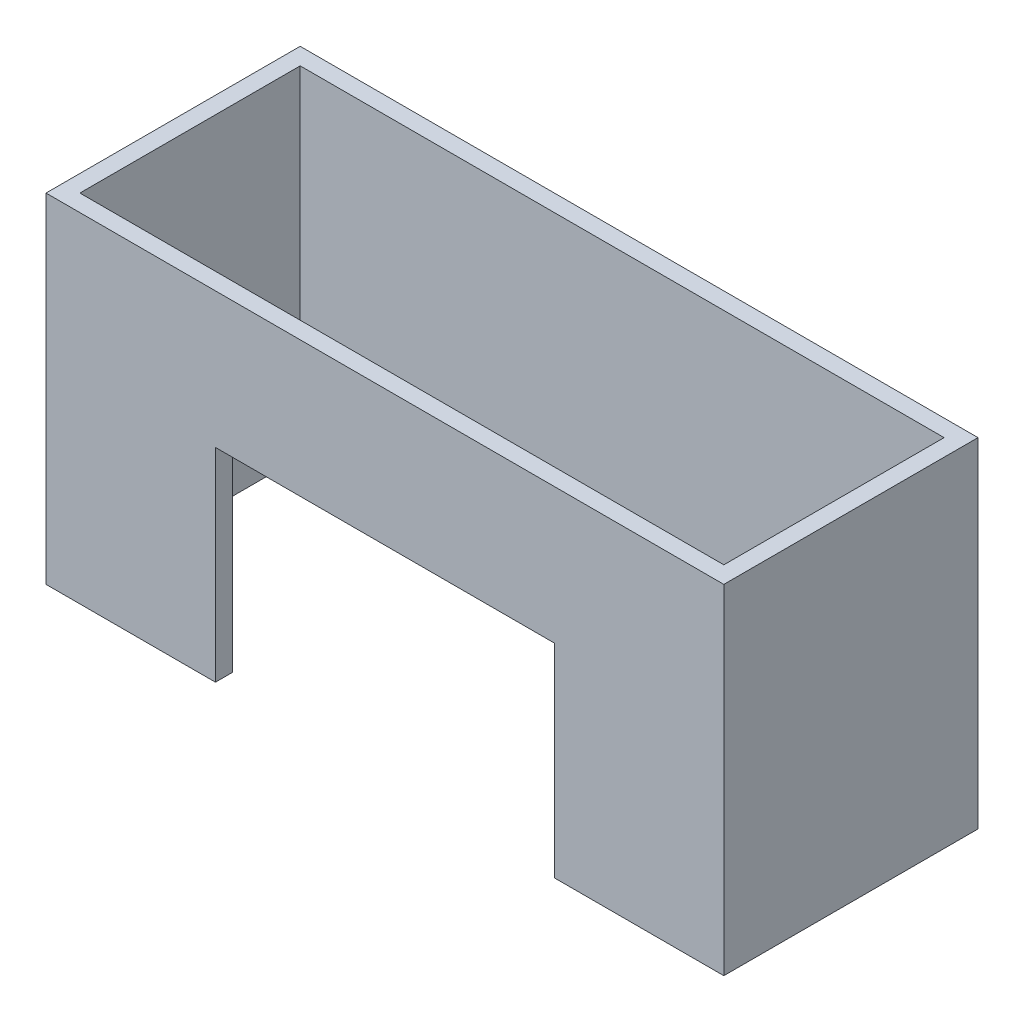
SolidWorks part; units mm, degrees
ref_plane "Front Plane" through (0, 0, 0) normal (0, 0, 1) x (1, 0, 0)
ref_plane "Top Plane" through (0, 0, 0) normal (0, 1, 0) x (1, 0, 0)
ref_plane "Right Plane" through (0, 0, 0) normal (1, 0, 0) x (0, 0, -1)
sketch "Sketch1" plane through (0, 0, 0) normal (0, 1, 0) x (1, 0, 0)
  line L1 (-200, 75) -> (200, 75)
  line L2 (-200, 75) -> (-200, -75)
  line L3 (-200, -75) -> (200, -75)
  line L4 (200, 75) -> (200, -75)
  line L5 (-200, 75) -> (200, -75) construction
  line L6 (-200, -75) -> (200, 75) construction
  point P0 (0, 0)
  dimension "D1" = 400
  dimension "D2" = 150
extrude "Boss-Extrude1" add sketch "Sketch1" along normal blind 200
sketch "Sketch2" plane through (0, 200, 0) normal (0, 1, 0) x (1, 0, 0)
  line L0 (200, 75) -> (-200, 75) construction
  line L1 (-190, 65) -> (190, 65)
  line L2 (-190, 65) -> (-190, -65)
  line L3 (-190, -65) -> (190, -65)
  line L4 (190, 65) -> (190, -65)
  line L5 (-190, 65) -> (190, -65) construction
  line L6 (-190, -65) -> (190, 65) construction
  line L7 (200, -75) -> (200, 75) construction
  point P0 (0, 0)
  dimension "D1" = 10
  dimension "D2" = 10
extrude "Cut-Extrude1" cut sketch "Sketch2" against normal blind 200
sketch "Sketch3" plane through (0, 0, 75) normal (0, 0, 1) x (1, 0, 0)
  line L0 (-200, 0) -> (200, 0) construction
  line L1 (-100, 120) -> (100, 120)
  line L2 (-100, 120) -> (-100, 0)
  line L3 (-100, 0) -> (100, 0)
  line L4 (100, 120) -> (100, 0)
  point P7 (0, 0)
  dimension "D1" = 200
  dimension "D2" = 120
extrude "Cut-Extrude2" cut sketch "Sketch3" against normal blind 20
